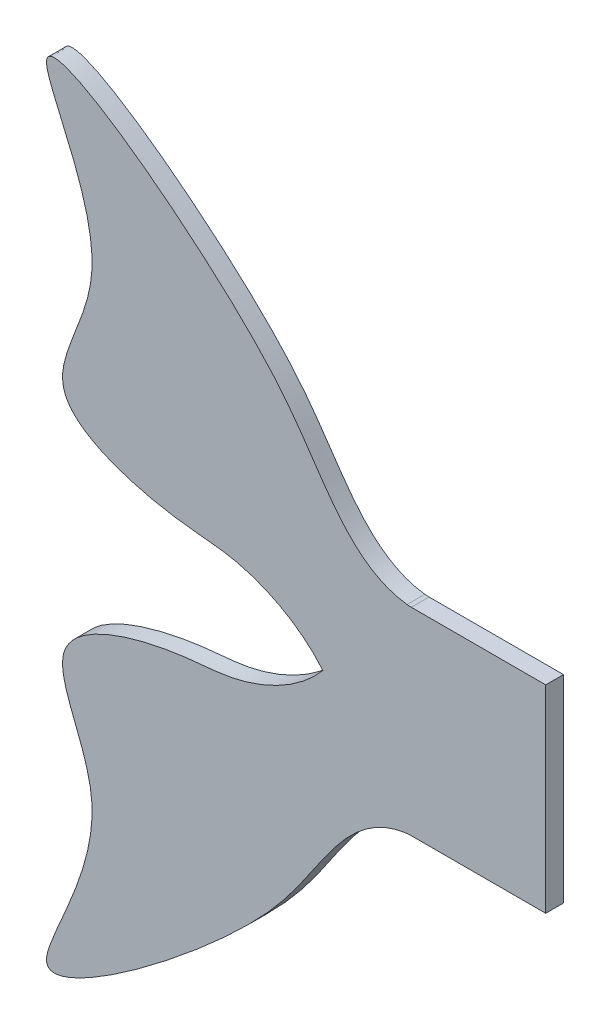
SolidWorks part; units mm, degrees
material "Silicon Rubber"
ref_plane "Front Plane" through (0, 0, 0) normal (0, 0, 1) x (1, 0, 0)
ref_plane "Top Plane" through (0, 0, 0) normal (0, 1, 0) x (1, 0, 0)
ref_plane "Right Plane" through (0, 0, 0) normal (1, 0, 0) x (0, 0, -1)
sketch "Sketch1" plane through (5.5797, 0, 0) normal (0, 0, 1) x (1, 0, 0)
  line L0 (-16.8315, 2.5344) -> (58.4186, 2.5344) construction
  line L1 (35.4186, 19.2344) -> (58.4186, 19.2344)
  line L2 (58.4186, 19.2344) -> (58.4186, -14.1656)
  line L3 (58.4186, -14.1656) -> (35.4186, -14.1656)
  spline S0 degree 3 poles (35.4186, 19.2344) (27.4693, 19.9613) (20.5282, 30.7105) (6.7777, 50.2099) (-40.8001, 85.7568) (-10.993, 43.005) (-30.6548, 18.7796) (-6.9082, 12.2112) (8.3948, 11.542) (16.8959, 7.2144) (20.7936, 2.5344) knots 0 0 0 0 0.125077 0.19256 0.451722 0.613213 0.726081 0.854298 0.895647 1 1 1 1
  spline S1 degree 3 poles (35.4186, -14.1656) (27.4693, -14.8924) (20.5282, -25.6417) (6.7777, -45.1411) (-40.8001, -80.688) (-10.993, -37.9362) (-30.6548, -13.7108) (-6.9082, -7.1424) (8.3948, -6.4732) (16.8959, -2.1456) (20.7936, 2.5344) knots 0 0 0 0 0.125077 0.19256 0.451722 0.613213 0.726081 0.854298 0.895647 1 1 1 1
  point P1 (-22.8521, -32.0914)
  point P2 (35.4186, 19.2344)
  point P4 (28.2559, 21.9503)
  point P5 (18.9077, 32.8973)
  point P6 (11.6779, 42.3493)
  point P7 (-25.8369, 68.4476)
  point P8 (-18.2296, 41.0056)
  point P9 (-22.8816, 21.6542)
  point P10 (-19.7018, 51.642)
  point P11 (-2.3396, 12.2089)
  point P12 (4.904, 11.3761)
  point P13 (-11.7109, 14.1078)
  point P14 (11.6827, 9.2633)
  point P15 (20.7936, 2.5344)
  point P18 (23.6553, 26.3422)
  point P19 (-22.774, 19.7305)
  point P23 (-23.7493, 50.4003)
  point P25 (0, 0)
  point P27 (-24.563, 69.5553)
  point P29 (-11.8158, 13.7376)
  point P31 (-18.2269, 41.0059)
  point P33 (-7.4517, 59.5717)
  point P35 (11.6791, 42.3505)
  point P37 (18.9074, 32.8971)
  point P38 (11.6779, 9.2553)
  point P39 (-22.8816, 21.6542)
  point P44 (-21.6509, 57.0455)
  point P55 (3.2804, 50.6493)
  point P59 (-15.2763, 15.3484)
  point P63 (-19.1731, -31.2047)
  point P65 (-12.6001, 63.3333)
  point P75 (-24.5075, 69.4436)
  dimension "D2" = 16.7
  dimension "D1" = 60.7989
  dimension "D3" = 23
extrude "Boss-Extrude1" add sketch "Sketch1" along normal mid plane 3
fillet "Fillet1" radius 6 2 edges at (40.9983, 19.2344, 0) (40.9983, -14.1656, 0)
